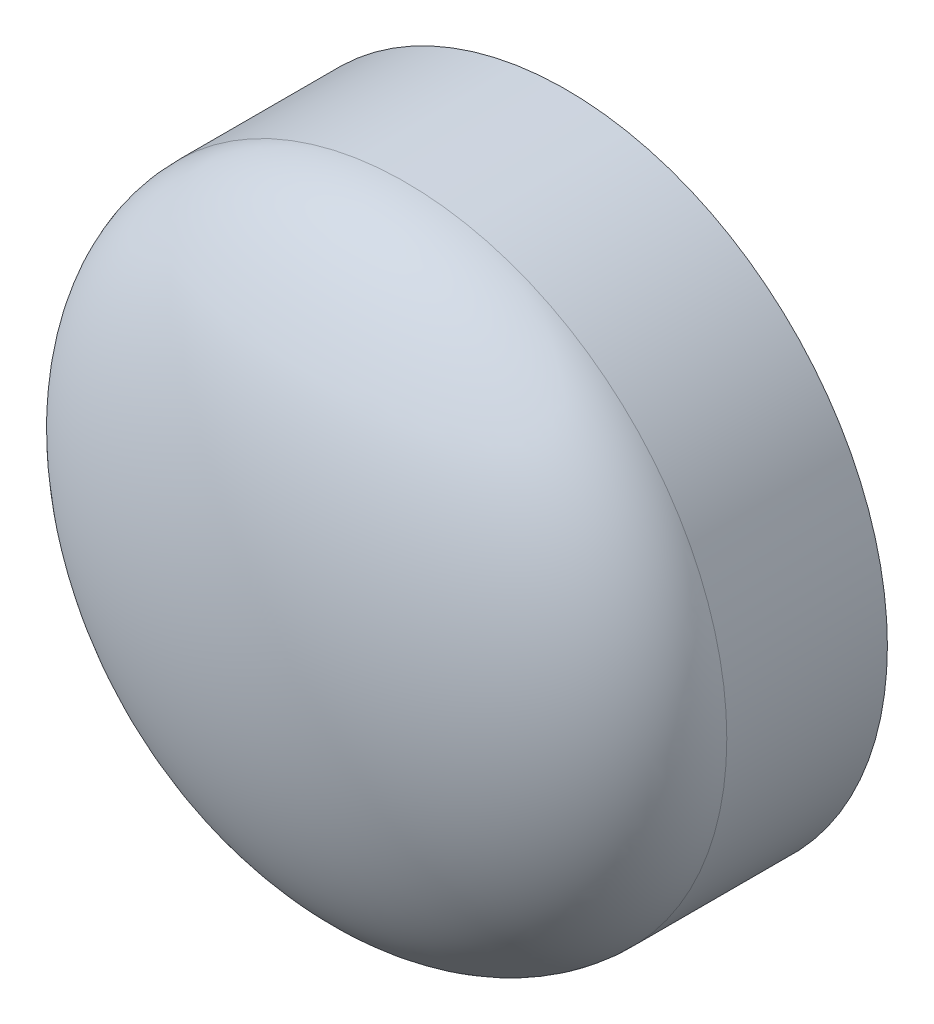
SolidWorks part; units mm, degrees
material "ABS PC"
ref_plane "Front Plane" through (0, 0, 0) normal (0, 0, 1) x (1, 0, 0)
ref_plane "Top Plane" through (0, 0, 0) normal (0, 1, 0) x (1, 0, 0)
ref_plane "Right Plane" through (0, 0, 0) normal (1, 0, 0) x (0, 0, -1)
sketch "Sketch1" plane through (0, 0, 0) normal (0, 0, 1) x (1, 0, 0)
  circle A0 centre (0, 0) radius 1.5875
extrude "Boss-Extrude1" add sketch "Sketch1" along normal blind 0.7937
dome "Dome1" faces to dome 1 distance 0.7937 reverse direction no elliptical dome yes face at (1.5875, 0, 0.7937) parameters "D1"=0.7937
